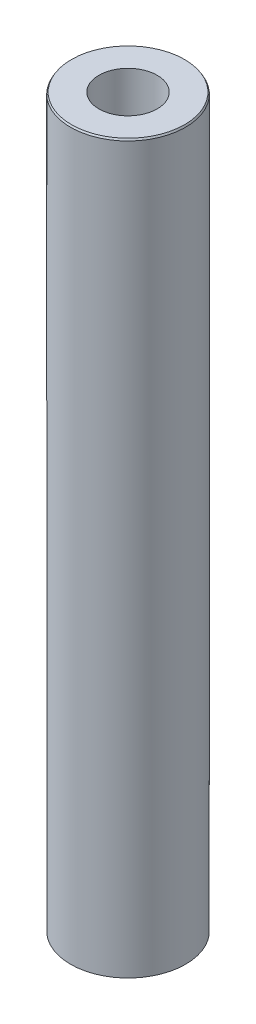
SolidWorks part; units mm, degrees
ref_plane "Front Plane" through (0, 0, 0) normal (0, 0, 1) x (1, 0, 0)
ref_plane "Top Plane" through (0, 0, 0) normal (0, 1, 0) x (1, 0, 0)
ref_plane "Right Plane" through (0, 0, 0) normal (1, 0, 0) x (0, 0, -1)
sketch "Sketch1" plane through (0, 0, 0) normal (0, 1, 0) x (1, 0, 0)
  circle A0 centre (0, 0) radius 7.5
  dimension "SHAFT_OD" = 15
extrude "Boss-Extrude1" add sketch "Sketch1" along normal blind 94.8706
sketch "Sketch2" plane through (0, 0, 0) normal (0, 1, 0) x (1, 0, 0)
  circle A0 centre (0, 0) radius 3.8021
  dimension "BORE_D" = 7.6042
extrude "Cut-Extrude1" cut sketch "Sketch2" along normal through all
chamfer "Chamfer1" distance 0.2236 angle 30 2 edges at (0, 94.8706, 7.5) (0, 0, 7.5) first distance on face at (0, 94.8706, 7.5) first distance on face at (0, 0, 3.8021)
